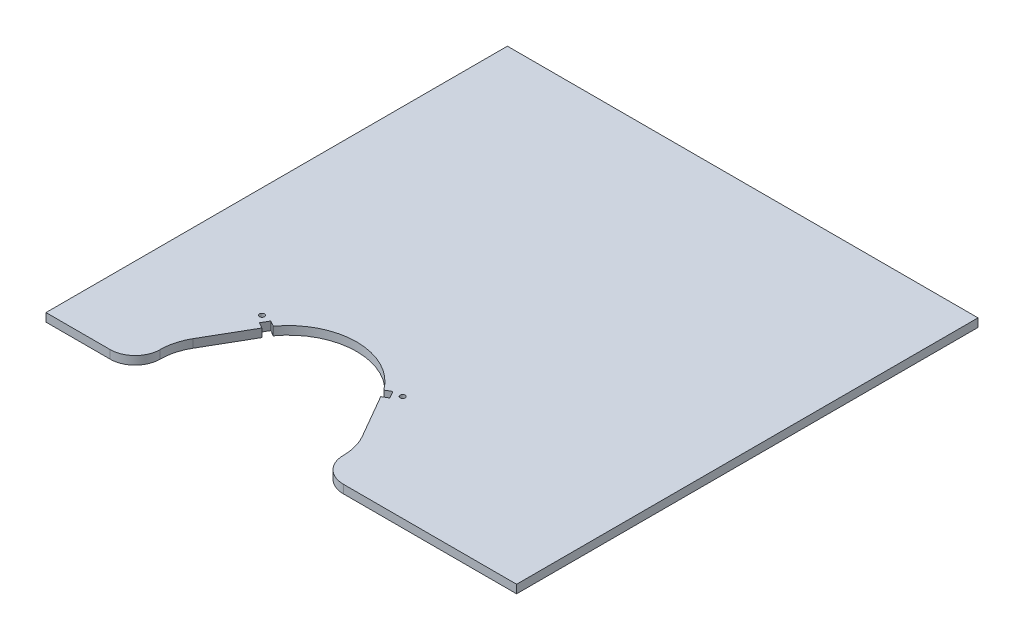
SolidWorks part; units mm, degrees
material "ABS PC"
ref_plane "Plan de face" through (0, 0, 0) normal (0, 0, 1) x (1, 0, 0)
ref_plane "Plan de dessus" through (0, 0, 0) normal (0, 1, 0) x (1, 0, 0)
ref_plane "Plan de droite" through (0, 0, 0) normal (1, 0, 0) x (0, 0, -1)
sketch "Esquisse1" plane through (0, 0, 0) normal (0, 1, 0) x (1, 0, 0)
  line L1 (-140.5, 31.9) -> (141.9979, 31.9)
  line L2 (-140.5, 31.9) -> (-140.5, -245.0829)
  line L3 (-140.5, -245.0829) -> (141.9979, -245.0829)
  line L4 (141.9979, 31.9) -> (141.9979, -245.0829)
  line L5 (38, -245.0829) -> (54.7016, -245.0829) construction
  line L6 (99.5, 31.9) -> (113.5, 31.9) construction
  arc A0 (-32, -23.5) -> (-95.029, -220.3153) centre (-32, -132) ccw construction
extrude "Boss.-Extru.1" add sketch "Esquisse1" along normal blind 5
sketch "Esquisse2" plane through (0, 0, 0) normal (0, 1, 0) x (1, 0, 0)
  line L3 (-65.1815, -184) -> (-68.6457, -182)
  line L4 (-68.6457, -182) -> (-71.1457, -186.3301)
  line L5 (-71.1457, -186.3301) -> (-67.6815, -188.3301)
  line L7 (-32, -132) -> (-32, -245.0829) construction
  line L8 (-65.1815, -184) -> (-67.6815, -188.3301) construction
  line L9 (-62.6323, -132) -> (62.6323, -132) construction
  line L10 (-32, -62.6323) -> (-32, 62.6323) construction
  line L11 (-67.6815, -188.3301) -> (-82.8539, -214.6094)
  line L13 (-65.1815, -184) -> (-61.7174, -186) construction
  line L14 (-32, -168.5125) -> (-32, -231.5125) construction
  line L16 (140.1, -245.0829) -> (-140.1, -245.0829) construction
  line L17 (-140.5, -245.0829) -> (141.9979, -245.0829) construction
  line L18 (1.1815, -184) -> (-2.2826, -186) construction
  line L20 (1.1815, -184) -> (3.6815, -188.3301) construction
  line L21 (3.6815, -188.3301) -> (18.8539, -214.6094)
  line L22 (7.1457, -186.3301) -> (3.6815, -188.3301)
  line L23 (4.6457, -182) -> (7.1457, -186.3301)
  line L24 (1.1815, -184) -> (4.6457, -182)
  line L25 (-69.8957, -184.1651) -> (-74.2258, -181.6651) construction
  line L26 (-102, -245.0829) -> (38, -245.0829)
  arc A1 (1.1815, -184) -> (-65.1815, -184) centre (-32, -208.0829) ccw
  arc A2 (-102, -245.0829) -> (-87, -230.0829) centre (-102, -230.0829) ccw
  arc A3 (-102, -245.0829) -> (-93.2863, -217.8734) centre (-102, -230.0829) ccw construction
  arc A4 (-87, -230.0829) -> (-82.8539, -214.6094) centre (-56.0531, -230.0829) cw
  arc A5 (23, -230.0829) -> (18.8539, -214.6094) centre (-7.9469, -230.0829) ccw
  arc A6 (38, -245.0829) -> (23, -230.0829) centre (38, -230.0829) cw
  circle A8 centre (-74.2258, -181.6651) radius 1.5
  circle A10 centre (10.2258, -181.6651) radius 1.5
  dimension "D4" = 41
  dimension "D8" = 5
  dimension "D9" = 3
  dimension "D1" = 4
  dimension "D2" = 52
  dimension "D3" = 37
  dimension "D5" = 90
  dimension "D6" = 5
  dimension "D7" = 30
extrude "Enlèv. mat.-Extru.2" cut sketch "Esquisse2" along normal through all
sketch "Esquisse3" plane through (0, 5, 0) normal (0, 1, 0) x (1, 0, 0)
  line L0 (-43.6093, -121.8429) -> (-36.5805, -137.9388)
  spline S0 degree 3 poles (259.3192, -1110.1176) (-417.1862, 235.5219) (-98.629, -194.1466) (-41.7351, -156.0551) (-41.3695, -155.7814) (-40.3208, -154.9029) (-39.696, -154.2528) (-38.8689, -153.1819) (-38.612, -152.8087) (-38.1363, -152.0291) (-37.9205, -151.6275) (-37.3411, -150.4003) (-37.0434, -149.5472) (-36.7214, -148.2184) (-36.6357, -147.7701) (-36.5052, -146.8774) (-36.4599, -146.4309) (-36.4039, -145.5376) (-36.3931, -145.0908) (-36.398, -144.4204) (-36.4039, -144.1969) (-36.4131, -143.7499) (-36.4173, -143.5265) (-37.0702, -106.8101) (-30.0085, -70.385) (-1030.1845, -25.1048) knots -9.338808 -9.338808 -9.338808 -9.338808 0.0625 0.0625 0.125 0.125 0.25 0.25 0.3125 0.3125 0.375 0.375 0.5 0.5 0.5625 0.5625 0.625 0.625 0.6875 0.6875 0.71875 0.71875 0.75 0.75 5.8528 5.8528 5.8528 5.8528 only from (-43.2724, -157) to (-36.5805, -137.9388)
  spline S1 degree 3 poles (-43.2724, -157) (-42.8739, -156.7891) (-42.4866, -156.5582) (-41.7351, -156.0551) (-41.3695, -155.7814) (-40.3208, -154.9029) (-39.696, -154.2528) (-38.8689, -153.1819) (-38.612, -152.8087) (-38.1363, -152.0291) (-37.9205, -151.6275) (-37.3411, -150.4003) (-37.0434, -149.5472) (-36.7214, -148.2184) (-36.6357, -147.7701) (-36.5052, -146.8774) (-36.4599, -146.4309) (-36.4039, -145.5376) (-36.3931, -145.0908) (-36.398, -144.4204) (-36.4039, -144.1969) (-36.4131, -143.7499) (-36.4173, -143.5265) (-36.4531, -141.5151) (-36.4664, -139.7274) (-36.5805, -137.9388) knots 0 0 0 0 0.0625 0.0625 0.125 0.125 0.25 0.25 0.3125 0.3125 0.375 0.375 0.5 0.5 0.5625 0.5625 0.625 0.625 0.6875 0.6875 0.71875 0.71875 0.75 0.75 1 1 1 1
  spline S2 degree 3 poles (-807.3976, -768.0821) (-207.7729, -356.7555) (-8.3852, -175.0827) (-57.4082, -99.0169) (-148.0414, -109.2326) (443.6615, -997.8773) knots -29.638124 -29.638124 -29.638124 -29.638124 0.5 0.5 17.046376 17.046376 17.046376 17.046376 only from (-38.6494, -128.5308) to (-41.788, -123.6579)
  spline S4 degree 3 poles (-38.6494, -128.5308) (-39.0465, -127.6427) (-39.508, -126.7915) (-40.5581, -125.1622) (-41.15, -124.3815) (-41.788, -123.6579) knots 0 0 0 0 0.5 0.5 1 1 1 1
  spline S5 degree 3 poles (-601.5613, -951.7121) (-116.3058, -360.4745) (0.6843, -155.5459) (-45.0773, -120.6633) (-45.465, -120.388) (-46.6525, -119.6032) (-47.4714, -119.1374) (-49.1602, -118.3132) (-50.0299, -117.9543) (-51.3722, -117.4954) (-51.8273, -117.3554) (-52.7403, -117.1048) (-53.1987, -116.9938) (-54.5796, -116.7027) (-55.5077, -116.5643) (-57.3789, -116.3974) (-58.3238, -116.3685) (-61.1694, -116.452) (-63.0237, -116.729) (-65.2886, -117.3484) (-65.7388, -117.4864) (-66.6338, -117.7911) (-67.0798, -117.9582) (-68.3938, -118.4955) (-69.2407, -118.9035) (-70.8796, -119.8131) (-71.6715, -120.315) (-72.8162, -121.1417) (-73.1906, -121.4295) (-73.9236, -122.0321) (-74.2806, -122.3458) (-75.3117, -123.3138) (-75.9498, -123.9992) (-77.1309, -125.4477) (-77.6748, -126.21) (-78.667, -127.8126) (-79.1156, -128.6557) (-79.7012, -129.9508) (-79.8821, -130.389) (-80.2197, -131.276) (-80.374, -131.7251) (-80.7027, -132.6174) (-80.8615, -133.0647) (-81.0687, -133.742) (-81.1361, -133.9681) (-81.2433, -134.4258) (-81.2806, -134.658) (-81.3797, -135.3572) (-81.4201, -135.8285) (-81.4694, -136.7776) (-81.4771, -137.2572) (-81.4503, -138.6941) (-81.3667, -139.6422) (-81.0729, -141.5194) (-80.863, -142.4485) (-80.3125, -144.287) (-79.977, -145.1777) (-79.1925, -146.901) (-78.7432, -147.7342) (-77.7262, -149.3415) (-77.1549, -150.12) (-75.9264, -151.5719) (-75.2661, -152.2499) (-73.8545, -153.5117) (-73.1023, -154.0965) (-71.5061, -155.1618) (-70.6797, -155.6314) (-68.9725, -156.4494) (-68.0915, -156.7974) (-66.7284, -157.2267) (-66.2654, -157.3546) (-65.3334, -157.5766) (-64.8656, -157.6706) (-63.4578, -157.91) (-62.5141, -158.0185) (-60.6172, -158.1455) (-59.664, -158.1628) (-57.7557, -158.179) (-56.8014, -158.1844) (-55.3741, -158.2823) (-54.899, -158.33) (-35.3598, -160.5329) (-16.7848, -168.613) (85.0426, 831.8111) knots -1.873626 -1.873626 -1.873626 -1.873626 0.015625 0.015625 0.03125 0.03125 0.0625 0.0625 0.09375 0.09375 0.109375 0.109375 0.125 0.125 0.15625 0.15625 0.1875 0.1875 0.25 0.25 0.265625 0.265625 0.28125 0.28125 0.3125 0.3125 0.34375 0.34375 0.359375 0.359375 0.375 0.375 0.40625 0.40625 0.4375 0.4375 0.46875 0.46875 0.484375 0.484375 0.5 0.5 0.515625 0.515625 0.523437 0.523437 0.53125 0.53125 0.546875 0.546875 0.5625 0.5625 0.59375 0.59375 0.625 0.625 0.65625 0.65625 0.6875 0.6875 0.71875 0.71875 0.75 0.75 0.78125 0.78125 0.8125 0.8125 0.84375 0.84375 0.859375 0.859375 0.875 0.875 0.90625 0.90625 0.9375 0.9375 0.96875 0.96875 0.984375 0.984375 1.611943 1.611943 1.611943 1.611943 only from (-43.6093, -121.8429) to (-53, -158.5394)
  spline S9 degree 3 poles (-43.6093, -121.8429) (-43.9623, -121.5334) (-44.3266, -121.2356) (-45.0773, -120.6633) (-45.465, -120.388) (-46.6525, -119.6032) (-47.4714, -119.1374) (-49.1602, -118.3132) (-50.0299, -117.9543) (-51.3722, -117.4954) (-51.8273, -117.3554) (-52.7403, -117.1048) (-53.1987, -116.9938) (-54.5796, -116.7027) (-55.5077, -116.5643) (-57.3789, -116.3974) (-58.3238, -116.3685) (-61.1694, -116.452) (-63.0237, -116.729) (-65.2886, -117.3484) (-65.7388, -117.4864) (-66.6338, -117.7911) (-67.0798, -117.9582) (-68.3938, -118.4955) (-69.2407, -118.9035) (-70.8796, -119.8131) (-71.6715, -120.315) (-72.8162, -121.1417) (-73.1906, -121.4295) (-73.9236, -122.0321) (-74.2806, -122.3458) (-75.3117, -123.3138) (-75.9498, -123.9992) (-77.1309, -125.4477) (-77.6748, -126.21) (-78.667, -127.8126) (-79.1156, -128.6557) (-79.7012, -129.9508) (-79.8821, -130.389) (-80.2197, -131.276) (-80.374, -131.7251) (-80.7027, -132.6174) (-80.8615, -133.0647) (-81.0687, -133.742) (-81.1361, -133.9681) (-81.2433, -134.4258) (-81.2806, -134.658) (-81.3797, -135.3572) (-81.4201, -135.8285) (-81.4694, -136.7776) (-81.4771, -137.2572) (-81.4503, -138.6941) (-81.3667, -139.6422) (-81.0729, -141.5194) (-80.863, -142.4485) (-80.3125, -144.287) (-79.977, -145.1777) (-79.1925, -146.901) (-78.7432, -147.7342) (-77.7262, -149.3415) (-77.1549, -150.12) (-75.9264, -151.5719) (-75.2661, -152.2499) (-73.8545, -153.5117) (-73.1023, -154.0965) (-71.5061, -155.1618) (-70.6797, -155.6314) (-68.9725, -156.4494) (-68.0915, -156.7974) (-66.7284, -157.2267) (-66.2654, -157.3546) (-65.3334, -157.5766) (-64.8656, -157.6706) (-63.4578, -157.91) (-62.5141, -158.0185) (-60.6172, -158.1455) (-59.664, -158.1628) (-57.7557, -158.179) (-56.8014, -158.1844) (-55.3741, -158.2823) (-54.899, -158.33) (-53.9497, -158.437) (-53.4753, -158.4942) (-53, -158.5394) knots 0 0 0 0 0.015625 0.015625 0.03125 0.03125 0.0625 0.0625 0.09375 0.09375 0.109375 0.109375 0.125 0.125 0.15625 0.15625 0.1875 0.1875 0.25 0.25 0.265625 0.265625 0.28125 0.28125 0.3125 0.3125 0.34375 0.34375 0.359375 0.359375 0.375 0.375 0.40625 0.40625 0.4375 0.4375 0.46875 0.46875 0.484375 0.484375 0.5 0.5 0.515625 0.515625 0.523437 0.523437 0.53125 0.53125 0.546875 0.546875 0.5625 0.5625 0.59375 0.59375 0.625 0.625 0.65625 0.65625 0.6875 0.6875 0.71875 0.71875 0.75 0.75 0.78125 0.78125 0.8125 0.8125 0.84375 0.84375 0.859375 0.859375 0.875 0.875 0.90625 0.90625 0.9375 0.9375 0.96875 0.96875 0.984375 0.984375 1 1 1 1
extrude "Enlèv. mat.-Extru.3" cut sketch "Esquisse3" against normal through all rebuild error yes
